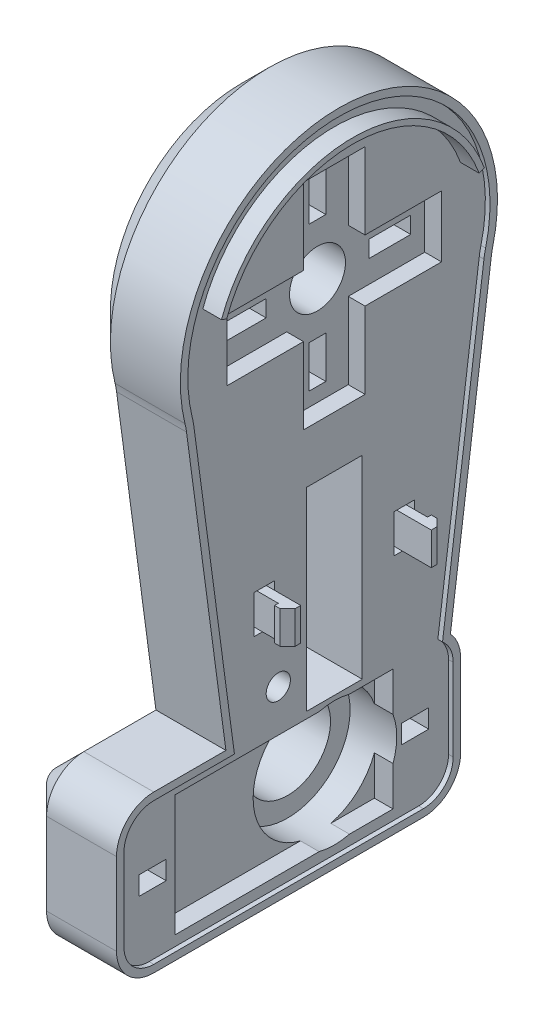
SolidWorks part; units mm, degrees
ref_plane "Front Plane" through (0, 0, 0) normal (0, 0, 1) x (1, 0, 0)
ref_plane "Top Plane" through (0, 0, 0) normal (0, 1, 0) x (1, 0, 0)
ref_plane "Right Plane" through (0, 0, 0) normal (1, 0, 0) x (0, 0, -1)
sketch "Sketch1" plane through (0, 0, 0) normal (1, 0, 0) x (0, 0, -1)
  line L0 (68.3427, -24.9297) -> (63.9535, -57.8487)
  line L1 (65.05, -60.6) -> (65.05, -69.4)
  line L2 (61.05, -73.4) -> (32.15, -73.4)
  line L3 (28.15, -69.4) -> (28.15, -60.6)
  line L4 (32.15, -56.6) -> (39.88, -56.6)
  line L5 (39.88, -56.6) -> (35.6573, -24.9297)
  arc A0 (35.4947, -24.0712) -> (68.5053, -24.0712) centre (52, -20) cw
  arc A1 (68.5053, -24.0712) -> (68.3427, -24.9297) centre (76.2725, -25.987) ccw
  arc A2 (63.9535, -57.8487) -> (65.05, -60.6) centre (61.05, -60.6) cw
  arc A3 (65.05, -69.4) -> (61.05, -73.4) centre (61.05, -69.4) cw
  arc A4 (32.15, -73.4) -> (28.15, -69.4) centre (32.15, -69.4) cw
  arc A5 (28.15, -60.6) -> (32.15, -56.6) centre (32.15, -60.6) cw
  arc A6 (35.6573, -24.9297) -> (35.4947, -24.0712) centre (27.7275, -25.987) ccw
extrude "Boss-Extrude1" add sketch "Sketch1" along normal blind 10.5 from offset 76.4 offset against normal yes
sketch "Sketch2" plane through (0, 0, 0) normal (1, 0, 0) x (0, 0, -1)
  line L0 (67.5497, -24.824) -> (63.1065, -58.1483)
  line L1 (64.25, -60.6) -> (64.25, -69.4)
  line L2 (61.05, -72.6) -> (32.15, -72.6)
  line L3 (28.95, -69.4) -> (28.95, -60.6)
  line L4 (32.15, -57.4) -> (40.7937, -57.4)
  line L5 (40.7937, -57.4) -> (36.4503, -24.824)
  arc A0 (36.2714, -23.8796) -> (67.7286, -23.8796) centre (52, -20) cw
  arc A1 (67.7286, -23.8796) -> (67.5497, -24.824) centre (76.2725, -25.987) ccw
  arc A2 (63.1065, -58.1483) -> (64.25, -60.6) centre (61.05, -60.6) cw
  arc A3 (64.25, -69.4) -> (61.05, -72.6) centre (61.05, -69.4) cw
  arc A4 (32.15, -72.6) -> (28.95, -69.4) centre (32.15, -69.4) cw
  arc A5 (28.95, -60.6) -> (32.15, -57.4) centre (32.15, -60.6) cw
  arc A6 (36.4503, -24.824) -> (36.2714, -23.8796) centre (27.7275, -25.987) ccw
extrude "Boss-Extrude2" add sketch "Sketch2" along normal blind 0.6 from offset 66.4 separate body offset against normal yes
combine bodies "Combine1" operation type subtract main body 101 bodies to subtract 102
chamfer "Chamfer1" distance 3 angle 45 5 edges at (-76.4, -41.3892, -66.1481) (-76.4, -40.7649, -37.7686) (-76.4, -24.4982, -68.4123) (-76.4, -24.4982, -35.5877) (-76.4, -3, -52)
chamfer "Chamfer2" distance 3 angle 45 8 edges at (-76.4, -56.6, -37.5283) (-76.4, -57.7716, -29.3216) (-76.4, -57.787, -63.8937) (-76.4, -65, -28.15) (-76.4, -65, -65.05) (-76.4, -72.2284, -29.3216) (-76.4, -72.2284, -63.8784) (-76.4, -73.4, -46.6)
sketch "Sketch3" plane through (0, 0, 0) normal (0, 0, 1) x (1, 0, 0)
  line L1 (-68.2, -31.5) -> (-65.9, -31.5)
  line L2 (-68.2, -31.5) -> (-68.2, -8.5)
  line L3 (-68.2, -8.5) -> (-65.9, -8.5)
  line L4 (-65.9, -31.5) -> (-65.9, -8.5)
extrude "Boss-Extrude3" add sketch "Sketch3" along normal blind 6.6 from offset 55.3 separate body offset against normal yes
combine bodies "Combine2" operation type subtract main body 103 bodies to subtract 104
sketch "Sketch4" plane through (0, 0, 0) normal (0, 0, 1) x (1, 0, 0)
  line L1 (-68.2, -23.3) -> (-65.9, -23.3)
  line L2 (-68.2, -23.3) -> (-68.2, -16.7)
  line L3 (-68.2, -16.7) -> (-65.9, -16.7)
  line L4 (-65.9, -23.3) -> (-65.9, -16.7)
extrude "Boss-Extrude4" add sketch "Sketch4" along normal blind 23 from offset 63.5 separate body offset against normal yes
combine bodies "Combine3" operation type subtract main body 105 bodies to subtract 106
sketch "Sketch5" plane through (0, 0, 0) normal (1, 0, 0) x (0, 0, -1)
  circle A0 centre (52, -20) radius 4.6
extrude "Boss-Extrude5" add sketch "Sketch5" along normal blind 2.3 from offset 68.2 separate body offset against normal yes
combine bodies "Combine4" operation type subtract main body 107 bodies to subtract 108
sketch "Sketch6" plane through (0, 0, 0) normal (1, 0, 0) x (0, 0, -1)
  circle A0 centre (52, -20) radius 6.1
extrude "Boss-Extrude6" add sketch "Sketch6" along normal blind 1.7 from offset 76.9 separate body offset against normal yes
combine bodies "Combine5" operation type subtract main body 109 bodies to subtract 110
sketch "Sketch7" plane through (0, 0, 0) normal (1, 0, 0) x (0, 0, -1)
  circle A0 centre (52, -20) radius 3
extrude "Boss-Extrude7" add sketch "Sketch7" along normal blind 7.2 from offset 75.3 separate body offset against normal yes
combine bodies "Combine6" operation type subtract main body 111 bodies to subtract 112
sketch "Sketch8" plane through (0, 0, 0) normal (0, 0, 1) x (1, 0, 0)
  line L1 (-74.2, -14.5) -> (-68.1, -14.5)
  line L2 (-74.2, -14.5) -> (-74.2, -13.4)
  line L3 (-74.2, -13.4) -> (-68.1, -13.4)
  line L4 (-68.1, -14.5) -> (-68.1, -13.4)
extrude "Boss-Extrude8" add sketch "Sketch8" along normal blind 1.8 from offset 52.9 separate body offset against normal yes
combine bodies "Combine7" operation type subtract main body 113 bodies to subtract 114
sketch "Sketch9" plane through (0, 0, 0) normal (0, 0, 1) x (1, 0, 0)
  line L1 (-74.2, -20.9) -> (-68.1, -20.9)
  line L2 (-74.2, -20.9) -> (-74.2, -19.1)
  line L3 (-74.2, -19.1) -> (-68.1, -19.1)
  line L4 (-68.1, -20.9) -> (-68.1, -19.1)
extrude "Boss-Extrude9" add sketch "Sketch9" along normal blind 1.1 from offset 46.5 separate body offset against normal yes
combine bodies "Combine8" operation type subtract main body 115 bodies to subtract 116
sketch "Sketch10" plane through (0, 0, 0) normal (0, 0, 1) x (1, 0, 0)
  line L1 (-74.2, -26.6) -> (-68.1, -26.6)
  line L2 (-74.2, -26.6) -> (-74.2, -25.5)
  line L3 (-74.2, -25.5) -> (-68.1, -25.5)
  line L4 (-68.1, -26.6) -> (-68.1, -25.5)
extrude "Boss-Extrude10" add sketch "Sketch10" along normal blind 1.8 from offset 52.9 separate body offset against normal yes
combine bodies "Combine9" operation type subtract main body 117 bodies to subtract 118
sketch "Sketch11" plane through (0, 0, 0) normal (0, 0, 1) x (1, 0, 0)
  line L1 (-74.2, -20.9) -> (-68.1, -20.9)
  line L2 (-74.2, -20.9) -> (-74.2, -19.1)
  line L3 (-74.2, -19.1) -> (-68.1, -19.1)
  line L4 (-68.1, -20.9) -> (-68.1, -19.1)
extrude "Boss-Extrude11" add sketch "Sketch11" along normal blind 1.1 from offset 58.6 separate body offset against normal yes
combine bodies "Combine10" operation type subtract main body 119 bodies to subtract 120
sketch "Sketch12" plane through (0, 0, 0) normal (0, 0, 1) x (1, 0, 0)
  line L1 (-75.4, -13.4) -> (-68.1, -13.4)
  line L2 (-75.4, -13.4) -> (-75.4, -10)
  line L3 (-75.4, -10) -> (-68.1, -10)
  line L4 (-68.1, -13.4) -> (-68.1, -10)
extrude "Boss-Extrude12" add sketch "Sketch12" along normal blind 1.8 from offset 52.9 separate body offset against normal yes
combine bodies "Combine11" operation type subtract main body 121 bodies to subtract 122
sketch "Sketch13" plane through (0, 0, 0) normal (0, 0, 1) x (1, 0, 0)
  line L1 (-75.4, -20.9) -> (-68.1, -20.9)
  line L2 (-75.4, -20.9) -> (-75.4, -19.1)
  line L3 (-75.4, -19.1) -> (-68.1, -19.1)
  line L4 (-68.1, -20.9) -> (-68.1, -19.1)
extrude "Boss-Extrude13" add sketch "Sketch13" along normal blind 3.4 from offset 45.4 separate body offset against normal yes
combine bodies "Combine12" operation type subtract main body 123 bodies to subtract 124
sketch "Sketch14" plane through (0, 0, 0) normal (0, 0, 1) x (1, 0, 0)
  line L1 (-75.4, -30) -> (-68.1, -30)
  line L2 (-75.4, -30) -> (-75.4, -26.6)
  line L3 (-75.4, -26.6) -> (-68.1, -26.6)
  line L4 (-68.1, -30) -> (-68.1, -26.6)
extrude "Boss-Extrude14" add sketch "Sketch14" along normal blind 1.8 from offset 52.9 separate body offset against normal yes
combine bodies "Combine13" operation type subtract main body 125 bodies to subtract 126
sketch "Sketch15" plane through (0, 0, 0) normal (0, 0, 1) x (1, 0, 0)
  line L1 (-75.4, -20.9) -> (-68.1, -20.9)
  line L2 (-75.4, -20.9) -> (-75.4, -19.1)
  line L3 (-75.4, -19.1) -> (-68.1, -19.1)
  line L4 (-68.1, -20.9) -> (-68.1, -19.1)
extrude "Boss-Extrude15" add sketch "Sketch15" along normal blind 3.4 from offset 62 separate body offset against normal yes
combine bodies "Combine14" operation type subtract main body 127 bodies to subtract 128
sketch "Sketch16" plane through (0, 0, 0) normal (1, 0, 0) x (0, 0, -1)
  line L0 (66.0954, -14.8697) -> (65.5316, -15.0749)
  line L1 (38.4684, -15.0749) -> (37.9046, -14.8697)
  arc A0 (37.9046, -14.8697) -> (66.0954, -14.8697) centre (52, -20) cw
  arc A1 (65.5316, -15.0749) -> (38.4684, -15.0749) centre (52, -20) ccw
extrude "Boss-Extrude16" add sketch "Sketch16" along normal blind 2.05 from offset 66.45 offset against normal yes
sketch "Sketch17" plane through (0, 0, 0) normal (0, 0, 1) x (1, 0, 0)
  line L1 (-70.4, -66) -> (-66.3, -66)
  line L2 (-70.4, -66) -> (-70.4, -64)
  line L3 (-70.4, -64) -> (-66.3, -64)
  line L4 (-66.3, -66) -> (-66.3, -64)
extrude "Boss-Extrude17" add sketch "Sketch17" along normal blind 2.9 from offset 62.125 separate body offset against normal yes
combine bodies "Combine15" operation type subtract main body 130 bodies to subtract 131
sketch "Sketch18" plane through (0, 0, 0) normal (0, 0, 1) x (1, 0, 0)
  line L1 (-70.4, -66) -> (-66.3, -66)
  line L2 (-70.4, -66) -> (-70.4, -64)
  line L3 (-70.4, -64) -> (-66.3, -64)
  line L4 (-66.3, -66) -> (-66.3, -64)
extrude "Boss-Extrude18" add sketch "Sketch18" along normal blind 2.9 from offset 33.975 separate body offset against normal yes
combine bodies "Combine16" operation type subtract main body 132 bodies to subtract 133
sketch "Sketch19" plane through (0, 0, 0) normal (0, 0, 1) x (1, 0, 0)
  line L1 (-68.4, -71.5) -> (-66.3, -71.5)
  line L2 (-68.4, -71.5) -> (-68.4, -58.5)
  line L3 (-68.4, -58.5) -> (-66.3, -58.5)
  line L4 (-66.3, -71.5) -> (-66.3, -58.5)
extrude "Boss-Extrude19" add sketch "Sketch19" along normal blind 23.4 from offset 58.3 separate body offset against normal yes
combine bodies "Combine17" operation type subtract main body 134 bodies to subtract 135
sketch "Sketch20" plane through (0, 0, 0) normal (1, 0, 0) x (0, 0, -1)
  circle A0 centre (52, -65) radius 6.7
extrude "Boss-Extrude20" add sketch "Sketch20" along normal blind 5.1 from offset 71.4 separate body offset against normal yes
combine bodies "Combine18" operation type subtract main body 136 bodies to subtract 137
sketch "Sketch21" plane through (0, 0, 0) normal (1, 0, 0) x (0, 0, -1)
  circle A0 centre (52, -65) radius 4.6
extrude "Boss-Extrude21" add sketch "Sketch21" along normal blind 5.8 from offset 76.9 separate body offset against normal yes
combine bodies "Combine19" operation type subtract main body 138 bodies to subtract 139
sketch "Sketch22" plane through (0, 0, 0) normal (0, 0, 1) x (1, 0, 0)
  line L1 (-74.6, -57.8) -> (-66.3, -57.8)
  line L2 (-74.6, -57.8) -> (-74.6, -37)
  line L3 (-74.6, -37) -> (-66.3, -37)
  line L4 (-66.3, -57.8) -> (-66.3, -37)
extrude "Boss-Extrude22" add sketch "Sketch22" along normal blind 6 from offset 55 separate body offset against normal yes
combine bodies "Combine20" operation type subtract main body 140 bodies to subtract 141
sketch "Sketch23" plane through (0, 0, 0) normal (1, 0, 0) x (0, 0, -1)
  circle A0 centre (46, -54) radius 2.3
extrude "Boss-Extrude23" add sketch "Sketch23" along normal blind 6 from offset 76.9 separate body offset against normal yes
combine bodies "Combine21" operation type subtract main body 142 bodies to subtract 143
sketch "Sketch24" plane through (0, 0, 0) normal (1, 0, 0) x (0, 0, -1)
  circle A0 centre (46, -54) radius 1.3
extrude "Boss-Extrude24" add sketch "Sketch24" along normal blind 4.65 from offset 70.95 separate body offset against normal yes
combine bodies "Combine22" operation type subtract main body 144 bodies to subtract 145
sketch "Sketch25" plane through (0, 0, 0) normal (0, 0, 1) x (1, 0, 0)
  line L1 (-70.4, -48.05) -> (-66.3, -48.05)
  line L2 (-70.4, -48.05) -> (-70.4, -43.95)
  line L3 (-70.4, -43.95) -> (-66.3, -43.95)
  line L4 (-66.3, -48.05) -> (-66.3, -43.95)
extrude "Boss-Extrude25" add sketch "Sketch25" along normal blind 2.2 from offset 60.6 separate body offset against normal yes
combine bodies "Combine23" operation type subtract main body 146 bodies to subtract 147
sketch "Sketch26" plane through (0, 0, 0) normal (0, 1, 0) x (1, 0, 0)
  line L0 (-70.6, 59) -> (-70.6, 60)
  line L1 (-70.6, 60) -> (-64.4, 60)
  line L2 (-64.4, 60) -> (-64.4, 60.4)
  line L3 (-64.4, 60.4) -> (-63.8, 60.4)
  line L4 (-63.8, 60.4) -> (-63, 59.6)
  line L5 (-63, 59.6) -> (-63, 59)
  line L6 (-63, 59) -> (-70.6, 59)
extrude "Boss-Extrude26" add sketch "Sketch26" along normal blind 3.5 from offset 47.75 offset against normal yes
sketch "Sketch27" plane through (0, 0, 0) normal (0, 0, 1) x (1, 0, 0)
  line L1 (-70.4, -48.05) -> (-66.3, -48.05)
  line L2 (-70.4, -48.05) -> (-70.4, -43.95)
  line L3 (-70.4, -43.95) -> (-66.3, -43.95)
  line L4 (-66.3, -48.05) -> (-66.3, -43.95)
extrude "Boss-Extrude27" add sketch "Sketch27" along normal blind 2.2 from offset 45.6 separate body offset against normal yes
combine bodies "Combine24" operation type subtract main body 149 bodies to subtract 150
sketch "Sketch28" plane through (0, 0, 0) normal (0, 1, 0) x (1, 0, 0)
  line L0 (-70.6, 45) -> (-70.6, 44)
  line L1 (-70.6, 44) -> (-64.4, 44)
  line L2 (-64.4, 44) -> (-64.4, 43.6)
  line L3 (-64.4, 43.6) -> (-63.8, 43.6)
  line L4 (-63.8, 43.6) -> (-63, 44.4)
  line L5 (-63, 44.4) -> (-63, 45)
  line L6 (-63, 45) -> (-70.6, 45)
extrude "Boss-Extrude28" add sketch "Sketch28" along normal blind 3.5 from offset 47.75 offset against normal yes
